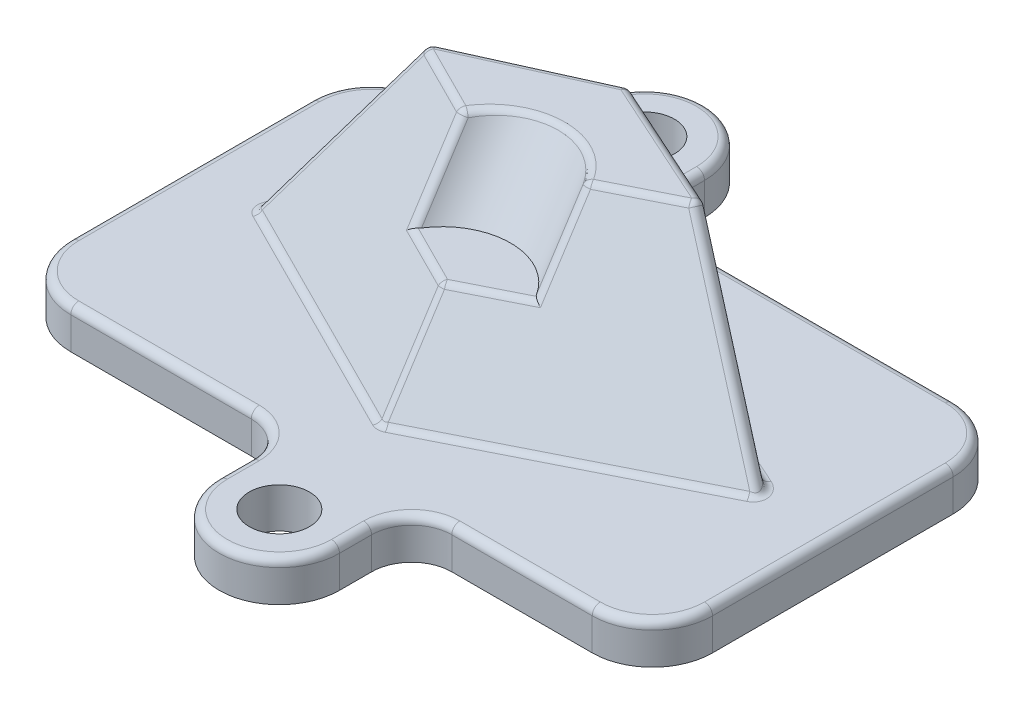
SolidWorks part; units mm, degrees
other "Markup2"
sketch "Sketch7" plane through (80, 53.1196, 78) normal (0.8478, 0.3519, 0.3968) x (0.438, -0.0429, -0.8979)
ref_plane "정면" through (0, 0, 0) normal (0, 0, 1) x (1, 0, 0)
ref_plane "윗면" through (0, 0, 0) normal (0, 1, 0) x (1, 0, 0)
ref_plane "우측면" through (0, 0, 0) normal (1, 0, 0) x (0, 0, -1)
sketch "Sketch1" plane through (0, 0, 0) normal (0, 1, 0) x (1, 0, 0)
  line L0 (-30, 63) -> (-30, 27) construction
  line L1 (-80, -45) -> (80, -45)
  line L2 (-80, -45) -> (-80, 45)
  line L3 (-80, 45) -> (80, 45)
  line L4 (80, -45) -> (80, 45)
  line L5 (-80, -45) -> (80, 45) construction
  line L6 (-80, 45) -> (80, -45) construction
  line L7 (-15, 63) -> (-15, 27)
  line L8 (-45, 63) -> (-45, 27)
  line L9 (5, -27) -> (5, -63) construction
  line L10 (20, -27) -> (20, -63)
  line L11 (-10, -27) -> (-10, -63)
  arc A0 (-15, 63) -> (-45, 63) centre (-30, 63) ccw
  arc A1 (-45, 27) -> (-15, 27) centre (-30, 27) ccw
  arc A2 (20, -27) -> (-10, -27) centre (5, -27) ccw
  arc A3 (-10, -63) -> (20, -63) centre (5, -63) ccw
  point P0 (0, 0)
  point P8 (-30, 45)
  point P15 (5, -45)
  point P20 (0, 0)
  dimension "D6" = 15
  dimension "D7" = 15
  dimension "D1" = 160
  dimension "D2" = 90
  dimension "D3" = 50
  dimension "D4" = 85
  dimension "D5" = 126
extrude "Boss-Extrude1" add sketch "Sketch1" along normal blind 10 contours A2 L10 L1 L4 L3 L7 A1 L8 L2 L11 | L8 A1 L7 L3 | L7 A0 L8 L3 | L10 A2 L11 L1 | L11 A3 L10 L1 region at (1.7708, 0, 0) region at (5, 0, 29.9213) region at (5, 0, 60.0787) region at (-30, 0, -60.0787) region at (-30, 0, -29.9213)
sketch "Sketch2" plane through (0, 10, 0) normal (0, 1, 0) x (1, 0, 0)
  line L0 (-81.5931, 0) -> (83.6799, 0) construction
  line L1 (0, 50.3958) -> (0, -79.402) construction
  line L2 (0, 29.3419) -> (65, 0)
  line L3 (65, 0) -> (0, -32.6581)
  line L4 (-65, 0) -> (0, -32.6581)
  line L5 (0, 29.3419) -> (-65, 0)
  circle A0 centre (-30, 63) radius 6.3395
  circle A1 centre (5, -63) radius 6.2105
  dimension "D1" = 62
  dimension "D2" = 130
extrude "Boss-Extrude2" add sketch "Sketch2" along normal blind 43 contours L5 L4 L3 L2
draft "Draft4" type of draft neutral plane draft angle 30 faces to draft 2 face at (-32.5, 31.5, 16.3291) face at (32.5, 31.5, 16.3291) neutral plane through (0, 10, 0) neutral plane normal (0, 1, 0) parameters "D1"=30
sketch "Sketch4" plane through (0, 53, 0) normal (0, 1, 0) x (1, 0, 0)
  circle A0 centre (0, -4.8747) radius 17
  dimension "D1" = 34
extrude "Cut-Extrude1" cut sketch "Sketch4" along direction (0, 0.8399, -0.5427) on the side against the normal blind 23
sketch "Sketch5" plane through (0, 10, 0) normal (0, 1, 0) x (1, 0, 0)
  circle A0 centre (-30, 63) radius 7.5
  circle A1 centre (5, -63) radius 7.5
  dimension "D1" = 15
  dimension "D2" = 15
extrude "Cut-Extrude2" cut sketch "Sketch5" against normal through all
fillet "Fillet3" radius 15 4 edges at (-80, 5, -45) (80, 5, -45) (80, 5, 45) (-80, 5, 45)
fillet "Fillet4" radius 10 4 edges at (20, 5, 45) (-10, 5, 45) (-45, 5, -45) (-15, 5, -45)
fillet "Fillet5" radius 2 37 edges at (-32.5, 10, -14.6709) (0, 31.5, -29.3419) (32.5, 10, -14.6709) (-17.9361, 53, -21.2453) (17.9361, 53, -21.2453) (0, 53, -12.1253) (-32.5, 10, 16.3291) (-50.4361, 31.5, -6.5743) (-25.5313, 53, -7.9531) (-15.1905, 43.3408, 3.4835) (-7.5952, 33.6817, 13.5407) (25.5313, 53, -7.9531) (50.4361, 31.5, -6.5743) (32.5, 10, 16.3291) (0, 21.8408, 25.0074) (7.5952, 33.6817, 13.5407) (15.1905, 43.3408, 3.4835) (-47.9289, 10, -47.9289) (-45, 10, -59) (-30, 10, -78) (-15, 10, -59) (-12.0711, 10, -47.9289) (30, 10, -45) (75.6066, 10, -40.6066) (80, 10, 0) (75.6066, 10, 40.6066) (47.5, 10, 45) (22.9289, 10, 47.9289) (20, 10, 59) (5, 10, 78) (-10, 10, 59) (-12.9289, 10, 47.9289) (-42.5, 10, 45) (-75.6066, 10, 40.6066) (-80, 10, 0) (-75.6066, 10, -40.6066) (-60, 10, -45)
